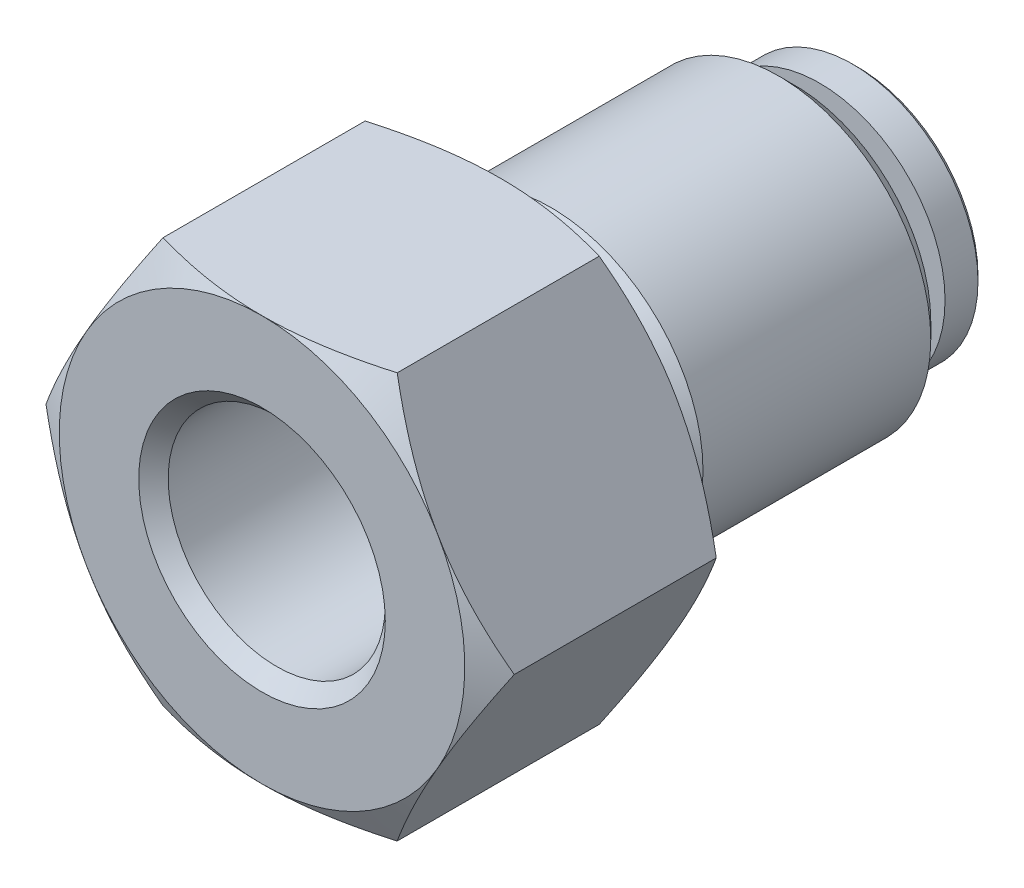
SolidWorks part; units mm, degrees
ref_plane "Front Plane" through (0, 0, 0) normal (0, 0, 1) x (1, 0, 0)
ref_plane "Top Plane" through (0, 0, 0) normal (0, 1, 0) x (1, 0, 0)
ref_plane "Right Plane" through (0, 0, 0) normal (1, 0, 0) x (0, 0, -1)
sketch "Sketch1" plane through (0, 0, 0) normal (0, 1, 0) x (1, 0, 0)
  line L0 (0, 0) -> (-8, 0)
  line L1 (-8, 0) -> (-9.6, 0.9238)
  line L2 (-9.6, 0.9238) -> (-9.6, 8.4762)
  line L3 (-9.6, 8.4762) -> (-8, 9.4)
  line L4 (-8, 9.4) -> (-5, 9.4)
  line L5 (-5, 9.4) -> (-5, 10.4)
  line L6 (-5, 10.4) -> (-6, 11.4)
  line L7 (-6, 11.4) -> (-6, 20.3865)
  line L8 (-6, 20.3865) -> (-5.3865, 21)
  line L9 (-5.3865, 21) -> (-3.3, 21)
  line L10 (-3.3, 21) -> (-3.3, 21.2)
  line L11 (-3.3, 21.2) -> (-3, 21.2)
  line L12 (-3, 21.2) -> (-3, 21.8)
  line L13 (-3, 21.8) -> (-3.2, 22)
  line L14 (-3.2, 22) -> (-4.95, 22)
  line L15 (-4.95, 22) -> (-4.95, 23.3)
  line L16 (-4.95, 23.3) -> (-4.75, 23.5)
  line L17 (-4.75, 23.5) -> (0, 23.5)
  line L18 (0, 23.5) -> (0, 0)
  line L19 (0, 23.5) -> (0, 0) construction
revolve "Revolve1" add sketch "Sketch1" angle 360 about L19 reverse direction yes
cosmetic thread "Cosmetic Thread1" parameters "D1"=8.6, "D2"=10.773
sketch "Sketch2" plane through (0, 0, 0) normal (0, 0, 1) x (1, 0, 0)
  line L0 (-16, -16) -> (16, -16)
  line L1 (16, -16) -> (16, 16)
  line L2 (16, 16) -> (-16, 16)
  line L3 (-16, 16) -> (-16, -16)
  line L4 (-9.2376, 0) -> (-4.6188, -8)
  line L5 (-4.6188, -8) -> (4.6188, -8)
  line L6 (4.6188, -8) -> (9.2376, 0)
  line L7 (9.2376, 0) -> (4.6188, 8)
  line L8 (4.6188, 8) -> (-4.6188, 8)
  line L9 (-4.6188, 8) -> (-9.2376, 0)
extrude "Cut-Extrude1" cut sketch "Sketch2" against normal blind 9.4
sketch "Sketch3" plane through (0, 0, 0) normal (1, 0, 0) x (0, 0, -1)
  line L0 (0, 0) -> (0, 4.864)
  line L1 (0, 4.864) -> (0.581, 4.283)
  line L2 (0.581, 4.283) -> (8.4, 4.283)
  line L3 (8.4, 4.283) -> (8.4, 1.5)
  line L4 (8.4, 1.5) -> (10, 1.5)
  line L5 (10, 1.5) -> (10.5, 2)
  line L6 (10.5, 2) -> (23.2, 2)
  line L7 (23.2, 2) -> (23.5, 2.3)
  line L8 (23.5, 2.3) -> (23.5, 0)
  line L9 (23.5, 0) -> (0, 0)
  line L10 (23.5, 0) -> (0, 0) construction
revolve "Cut-Revolve1" cut sketch "Sketch3" angle 360 about L10 reverse direction yes
cosmetic thread "Cosmetic Thread2" parameters "D1"=7.5, "D2"=9.728
ref_plane "Plane1" through (0, 0, -12.4) normal (0, 0, 1) x (1, 0, 0)
ref_plane "ANBAU XY" through (0, 0, 0) normal (0, 0, -1) x (-1, 0, 0)
ref_plane "ANBAU XZ" through (0, 0, 0) normal (0, 1, 0) x (1, 0, 0)
ref_plane "ANBAU YZ" through (0, 0, 0) normal (1, 0, 0) x (0, 0, -1)
ref_axis "ANBAU X" through (-80.9, 0, 0) along (1, 0, 0)
ref_axis "ANBAU Y" through (0, 50, 0) along (0, -1, 0)
ref_axis "ANBAU Z" through (0, 0, -80.9) along (0, 0, 1)
sketch3d "ANBAU"
  point P0 (0, 0, 0)
ref_plane "IP1 XY" through (0, 0, -12.4) normal (0, 0, 1) x (1, 0, 0)
ref_plane "IP1 XZ" through (0, 0, 0) normal (0, -1, 0) x (-1, 0, 0)
ref_plane "IP1 YZ" through (0, 0, 0) normal (1, 0, 0) x (0, 0, -1)
ref_axis "IP1 X" through (-80.9, 0, -12.4) along (1, 0, 0)
ref_axis "IP1 Y" through (0, -50, -12.4) along (0, 1, 0)
ref_axis "IP1 Z" through (0, 0, 80.9) along (0, 0, -1)
sketch3d "IP1"
  point P0 (0, 0, -12.4)
